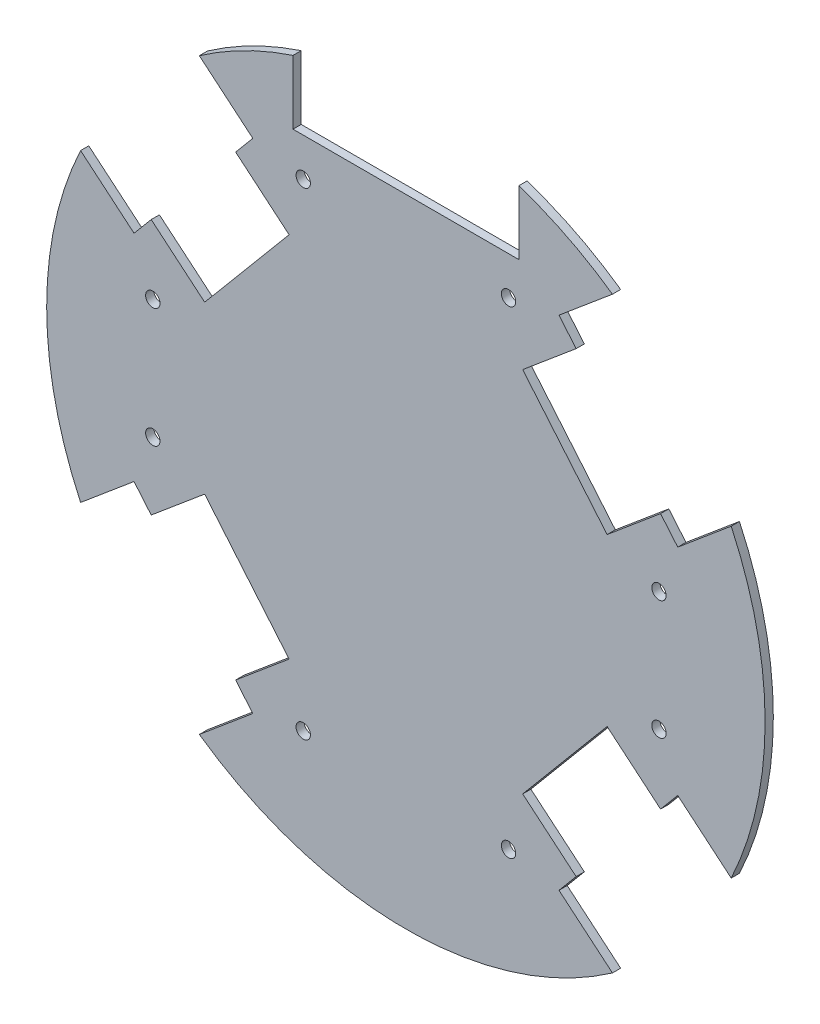
SolidWorks part; units mm, degrees
ref_plane "Front Plane" through (0, 0, 0) normal (0, 0, 1) x (1, 0, 0)
ref_plane "Top Plane" through (0, 0, 0) normal (0, 1, 0) x (1, 0, 0)
ref_plane "Right Plane" through (0, 0, 0) normal (1, 0, 0) x (0, 0, -1)
sketch "Sketch1" plane through (0, 0, 0) normal (0, 0, 1) x (1, 0, 0)
  circle A1 centre (0, 0) radius 87.5
  dimension "D1" = 87.5
extrude "Boss-Extrude1" add sketch "Sketch1" against normal blind 2
sketch "Sketch3" plane through (0, 0, 0) normal (0, 0, 1) x (1, 0, 0)
  line L0 (-87.5, 0) -> (0, 0) construction
  line L1 (0, 0) -> (-38.7294, 32.4978) construction
  line L2 (-49.014, 20.2411) -> (-28.4448, 44.7546)
  line L3 (-49.014, 20.2411) -> (-62.0368, 31.1685)
  line L4 (-62.0368, 31.1685) -> (-66.2149, 26.1892)
  line L5 (-66.2149, 26.1892) -> (-79.2377, 37.1166)
  line L6 (-79.2377, 37.1166) -> (-50.3122, 71.5886) construction
  line L7 (-50.3122, 71.5886) -> (-37.2895, 60.6612)
  line L8 (-37.2895, 60.6612) -> (-41.4676, 55.6819)
  line L9 (-41.4676, 55.6819) -> (-28.4448, 44.7546)
  line L10 (-62.0368, 31.1685) -> (-41.4676, 55.6819) construction
  line L11 (-38.7294, 32.4978) -> (-51.7522, 43.4252) construction
  line L12 (-51.7522, 43.4252) -> (-64.7749, 54.3526) construction
  line L13 (-61.6451, 14.5223) -> (-25.0062, 58.1868) construction
  circle A0 centre (0, 0) radius 87.5 construction
  arc A1 (-50.3122, 71.5886) -> (-79.2377, 37.1166) centre (0, 0) ccw
  arc A2 (-87.5, 0) -> (87.5, 0) centre (0, 0) ccw
  circle A3 centre (-61.6451, 14.5223) radius 1.75
  circle A4 centre (-25.0062, 58.1868) radius 1.75
  point P19 (-43.3257, 36.3546)
  circle M14 centre (0, 0) radius 87.5
  dimension "D8" = 3.5
  dimension "D1" = 40
  dimension "D2" = 32
  dimension "D3" = 45
  dimension "D4" = 17
  dimension "D5" = 17
  dimension "D6" = 57
  dimension "D7" = 6
extrude "Cut-Extrude1" cut sketch "Sketch3" against normal through all contours L9 L8 L7 L5 L4 L3 L2 M14 | A3 | A4 region at (-53.6644, 45.0298, 0)
mirror "Mirror1" about plane through (0, 0, 0) normal (1, 0, 0) of "Cut-Extrude1" second plane through (0, 0, 0) second plane normal (0, 1, 0)
sketch "Sketch4" plane through (0, 0, 0) normal (0, 0, 1) x (1, 0, 0)
  line L1 (-27.5, 107.5) -> (27.5, 107.5)
  line L2 (-27.5, 107.5) -> (-27.5, 67.5)
  line L3 (-27.5, 67.5) -> (27.5, 67.5)
  line L4 (27.5, 107.5) -> (27.5, 67.5)
  line L5 (-27.5, 107.5) -> (27.5, 67.5) construction
  line L6 (-27.5, 67.5) -> (27.5, 107.5) construction
  arc A0 (50.3122, 71.5886) -> (-50.3122, 71.5886) centre (0, 0) ccw construction
  point P0 (0, 87.5)
  dimension "D1" = 55
  dimension "D2" = 40
extrude "Cut-Extrude2" cut sketch "Sketch4" against normal through all and the other way through all
